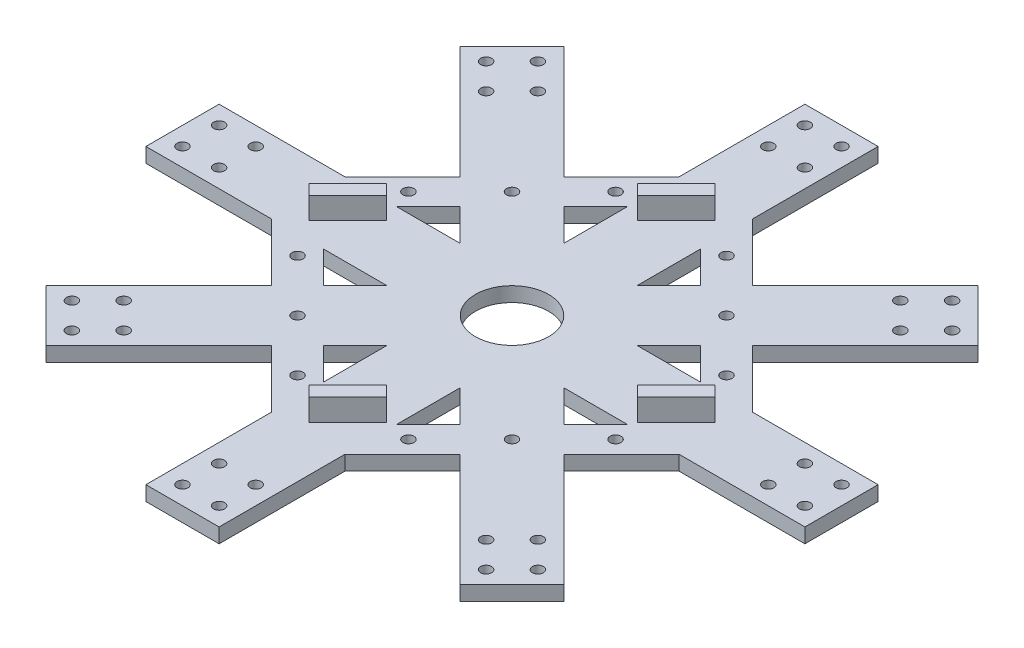
SolidWorks part; units mm, degrees
ref_plane "Front Plane" through (0, 0, 0) normal (0, 0, 1) x (1, 0, 0)
ref_plane "Top Plane" through (0, 0, 0) normal (0, 1, 0) x (1, 0, 0)
ref_plane "Right Plane" through (0, 0, 0) normal (1, 0, 0) x (0, 0, -1)
sketch "Sketch1" plane through (0, 0, 0) normal (0, 1, 0) x (1, 0, 0)
  line L0 (20, 100) -> (100, 100)
  line L1 (0, 0) -> (20, 0)
  line L2 (0, 0) -> (0, 80)
  line L3 (0, 180) -> (20, 180)
  line L4 (20, 0) -> (20, 80)
  line L5 (-80, 100) -> (0, 100)
  line L6 (-80, 100) -> (-80, 80)
  line L7 (-80, 80) -> (0, 80)
  line L8 (100, 100) -> (100, 80)
  line L9 (0, 100) -> (0, 180)
  line L10 (20, 80) -> (100, 80)
  line L11 (20, 100) -> (20, 180)
  line L12 (-40, 100) -> (0, 140) construction
  line L13 (20, 140) -> (60, 100) construction
  line L14 (60, 80) -> (20, 40) construction
  line L15 (0, 40) -> (-40, 80) construction
  line L16 (0, 48.4853) -> (-31.5147, 80)
  line L17 (51.5147, 80) -> (20, 48.4853)
  line L18 (20, 131.5147) -> (51.5147, 100)
  line L19 (-31.5147, 100) -> (0, 131.5147)
  line L20 (0, 34.3431) -> (-45.6569, 80)
  line L21 (65.6569, 80) -> (20, 34.3431)
  line L22 (20, 145.6569) -> (65.6569, 100)
  line L23 (-45.6569, 100) -> (0, 145.6569)
  line L24 (-2.8284, 37.1716) -> (-42.8284, 77.1716) construction
  line L25 (-35.7574, 95.7574) -> (4.2426, 135.7574) construction
  line L26 (15.7574, 135.7574) -> (55.7574, 95.7574) construction
  line L27 (55.7574, 84.2426) -> (15.7574, 44.2426) construction
  line L28 (4.2426, 44.2426) -> (-35.7574, 84.2426) construction
  line L29 (62.8284, 77.1716) -> (22.8284, 37.1716) construction
  line L30 (22.8284, 142.8284) -> (62.8284, 102.8284) construction
  line L31 (-42.8284, 102.8284) -> (-2.8284, 142.8284) construction
  circle A0 centre (10, 90) radius 1.5
  point P24 (10, 180)
  point P25 (100, 90)
  dimension "D13" = 3
  dimension "D2" = 180
  dimension "D3" = 180
  dimension "D4" = 20
  dimension "D7" = 40
  dimension "D8" = 40
  dimension "D9" = 40
  dimension "D10" = 40
  dimension "D11" = 6
  dimension "D12" = 4
extrude "Base" add sketch "Sketch1" along normal blind 4 contours L0 L11 L3 L9 L5 L6 L7 L2 L1 L4 L10 L8 | L23 L5 L19 L9 | L22 L11 L18 L0 | L20 L2 L16 L7 | L21 L10 L17 L4 region at (35.7574, 0, -97.4544) region at (39.5089, 0, -119.5089) region at (39.5089, 0, -60.4911) region at (-19.5089, 0, -119.5089) region at (-19.5089, 0, -60.4911)
sketch "Sketch2" plane through (0, 4, 0) normal (0, 1, 0) x (1, 0, 0)
  line L0 (40.5824, 165.4836) -> (-65.4836, 59.4176) construction
  line L1 (-65.4836, 59.4176) -> (-20.5824, 14.5164) construction
  line L2 (-20.5824, 14.5164) -> (85.4836, 120.5824) construction
  line L3 (85.4836, 120.5824) -> (40.5824, 165.4836) construction
  line L4 (15.3033, 50.402) -> (4.6967, 39.7954)
  line L5 (-22.7601, 57.2399) -> (42.1744, 122.1744) construction
  line L6 (4.6967, 39.7954) -> (7.5251, 36.967)
  line L7 (20, 145.6569) -> (65.6569, 100) construction
  line L8 (0, 34.3431) -> (-45.6569, 80) construction
  line L9 (51.4142, 48.5858) -> (-13.5858, 113.5858) construction
  line L10 (7.5251, 36.967) -> (18.1317, 47.5736)
  line L11 (18.1317, 47.5736) -> (15.3033, 50.402)
  line L12 (12.4749, 143.033) -> (1.8683, 132.4264)
  line L13 (51.5147, 80) -> (20, 48.4853) construction
  line L14 (49.598, 84.6967) -> (60.2046, 95.3033)
  line L15 (60.2046, 95.3033) -> (63.033, 92.4749)
  line L16 (63.033, 92.4749) -> (52.4264, 81.8683)
  line L17 (52.4264, 81.8683) -> (49.598, 84.6967)
  line L18 (15.3033, 140.2046) -> (12.4749, 143.033)
  line L19 (4.6967, 129.598) -> (15.3033, 140.2046)
  line L20 (1.8683, 132.4264) -> (4.6967, 129.598)
  line L21 (-43.033, 87.5251) -> (-32.4264, 98.1317)
  line L22 (-40.2046, 84.6967) -> (-43.033, 87.5251)
  line L23 (-29.598, 95.3033) -> (-40.2046, 84.6967)
  line L24 (-32.4264, 98.1317) -> (-29.598, 95.3033)
  point P7 (42.8284, 122.8284)
  point P11 (-22.8284, 57.1716)
  point P12 (63.033, 143.033)
  point P16 (35.7574, 64.2426)
  point P17 (-12.4506, 112.4506)
  point P20 (32.4506, 67.5494)
  point P22 (10, 45.0987)
  point P26 (54.9013, 90)
  point P27 (10, 90)
  dimension "D1" = 150
  dimension "D2" = 63.5
  dimension "D3" = 15
  dimension "D4" = 4
extrude "BatteryClip" add sketch "Sketch2" along normal blind 6
ref_axis "RotationalAxis" through (10, 4, -90) along (0, -1, 0)
ref_plane "Plane3" through (50, 0, -50) normal (-0.7071, 0, 0.7071) x (0.7071, 0, 0.7071)
sketch "Sketch6" plane through (0, 0, 0) normal (0, -1, 0) x (1, 0, 0)
  line L0 (66.5685, -160.7107) -> (10, -104.1421)
  line L1 (-60.7107, -33.4315) -> (-46.5685, -19.2893)
  line L2 (-46.5685, -19.2893) -> (10, -75.8579)
  line L3 (66.5685, -160.7107) -> (80.7107, -146.5685)
  line L4 (-46.5685, -160.7107) -> (10, -104.1421)
  line L5 (80.7107, -33.4315) -> (66.5685, -19.2893)
  line L6 (66.5685, -19.2893) -> (10, -75.8579)
  line L7 (-60.7107, -146.5685) -> (-46.5685, -160.7107)
  line L8 (10, -90) -> (75.7432, -155.7432) construction
  line L10 (51.5556, -48.4444) -> (48.4444, -51.5556) construction
  line L11 (-33.5468, -133.5468) -> (10, -90) construction
  line L12 (-4.1421, -90) -> (-60.7107, -146.5685)
  line L13 (10, -75.8579) -> (2.9289, -82.9289) construction
  line L14 (2.9289, -82.9289) -> (-4.1421, -90) construction
  line L15 (-4.1421, -90) -> (-60.7107, -33.4315)
  line L16 (2.9289, -97.0711) -> (-4.1421, -90) construction
  line L17 (10, -104.1421) -> (2.9289, -97.0711) construction
  line L18 (24.1421, -90) -> (80.7107, -33.4315)
  line L19 (10, -104.1421) -> (17.0711, -97.0711) construction
  line L20 (17.0711, -97.0711) -> (24.1421, -90) construction
  line L21 (17.0711, -82.9289) -> (45.7458, -54.2542) construction
  line L22 (10, -90) -> (17.0711, -82.9289) construction
  line L23 (24.1421, -90) -> (80.7107, -146.5685)
  line L24 (17.0711, -82.9289) -> (24.1421, -90) construction
  line L25 (10, -75.8579) -> (17.0711, -82.9289) construction
  point P15 (73.6396, -26.3604)
  point P17 (73.6396, -153.6396)
  dimension "D1" = 180
  dimension "D2" = 20
extrude "Boss-Extrude1" add sketch "Sketch6" against normal up to surface (4 mm away) up to face at (10, 4, -90)
hole_wizard "Ø3.0mm Dowel Hole2" positions "3DSketch2" profile "Sketch5" hole size "Ø3.0" standard "ANSI Metric" end condition through all
sketch3d "3DSketch2"
  line L1 (10, 4, 0) -> (10, 4, -50000) construction
  line L2 (0, 4, 0) -> (20, 4, 0) construction
  line L3 (0, 4, -180) -> (20, 4, -180) construction
  line L4 (-65, 4, -90) -> (49935, 4, -90) construction
  line L5 (-80, 4, -100) -> (-80, 4, -80) construction
  line L6 (100, 4, -100) -> (100, 4, -80) construction
  line L7 (-8.7317, 4, -71.2683) -> (30646.88, 4, -30726.88) construction
  line L11 (-5.1508, 4, -46.565) -> (-33.435, 4, -74.8492) construction
  line L13 (0, 4, -48.4853) -> (-8.6863, 4, -57.1716) construction
  line L14 (-46.5685, 4, -19.2893) -> (-60.7107, 4, -33.4315) construction
  line L15 (-15.7574, 4, -50.1005) -> (-46.5685, 4, -19.2893) construction
  line L16 (-53.6396, 4, -33.4315) -> (-46.5685, 4, -40.5025) construction
  line L17 (-46.5685, 4, -40.5025) -> (-39.4975, 4, -33.4315) construction
  line L18 (-39.4975, 4, -33.4315) -> (-46.5685, 4, -26.3604) construction
  line L19 (-46.5685, 4, -26.3604) -> (-53.6396, 4, -33.4315) construction
  line L21 (-60.7107, 4, -33.4315) -> (-29.8995, 4, -64.2426) construction
  line L22 (66.5685, 4, -160.7107) -> (80.7107, 4, -146.5685) construction
  point P0 (5, 4, -5)
  point P2 (5, 4, -15)
  point P4 (15, 4, -15)
  point P6 (15, 4, -5)
  point P17 (10, 4, 0)
  point P20 (10, 4, -180)
  point P27 (-80, 4, -90)
  point P30 (100, 4, -90)
  point P44 (-5.1508, 4, -46.565)
  point P46 (-19.2929, 4, -60.7071)
  point P48 (-33.435, 4, -74.8492)
  point P74 (-53.6396, 4, -33.4315)
  point P76 (-46.5685, 4, -40.5025)
  point P78 (-39.4975, 4, -33.4315)
  point P80 (-46.5685, 4, -26.3604)
  point P98 (73.6396, 4, -153.6396)
  point P100 (-53.6396, 4, -26.3604)
  dimension "D1" = 5
  dimension "D6" = 40
  dimension "D2" = 10
  dimension "D3" = 10
  dimension "D4" = 5
  dimension "D5" = 5
  dimension "D7" = 10
  dimension "D8" = 10
  dimension "D9" = 5
  dimension "D10" = 5
sketch "Sketch5" plane through (5, 4, -5) normal (1, 0, 0) x (0, 0, 1)
  line L0 (0, 0) -> (0, 4)
  line L1 (0, 4) -> (1.5, 4)
  line L2 (1.5, 4) -> (1.5, 0)
  line L5 (1.5, 0) -> (0, 0)
  line L11 (0, -6.35) -> (0, 107.95) construction
  dimension "Thru Hole Dia." = 3
  dimension "Thru Hole Depth" = 4
pattern_circular "CirPattern2" count 4 over 360 about axis through (10, 4, -90) along (0, -1, 0) of "Ø3.0mm Dowel Hole2"
sketch "Sketch7" plane through (0, 4, 0) normal (0, 1, 0) x (1, 0, 0)
  circle A0 centre (10, 90) radius 10
  dimension "D1" = 20
extrude "Refrerence" cut sketch "Sketch7" against normal blind 10
